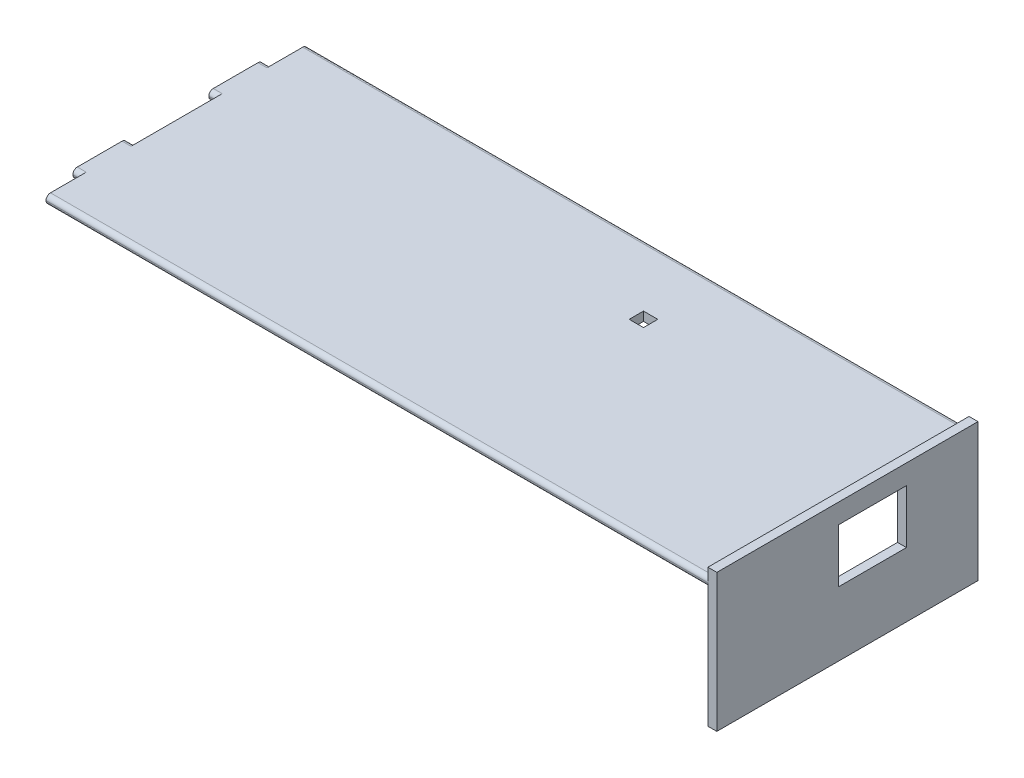
SolidWorks part; units mm, degrees
ref_plane "前视基准面" through (0, 0, 0) normal (0, 0, 1) x (1, 0, 0)
ref_plane "上视基准面" through (0, 0, 0) normal (0, 1, 0) x (1, 0, 0)
ref_plane "右视基准面" through (0, 0, 0) normal (1, 0, 0) x (0, 0, -1)
other "Configuration Table"
sketch "草图1" plane through (0, 0, 0) normal (0, 1, 0) x (1, 0, 0)
  line L1 (-87.0065, 44.1075) -> (97.9935, 44.1075)
  line L2 (-87.0065, 44.1075) -> (-87.0065, -28.8925)
  line L3 (-87.0065, -28.8925) -> (97.9935, -28.8925)
  line L4 (97.9935, 44.1075) -> (97.9935, -28.8925)
  dimension "D1" = 185
  dimension "D2" = 73
extrude "凸台-拉伸1" add sketch "草图1" along normal blind 2.5
sketch "草图2" plane through (-87.0065, 0, 0) normal (-1, 0, 0) x (0, 0, 1)
  line L0 (-44.1075, 2.5) -> (28.8925, 2.5) construction
  line L1 (-34.1075, 2.5) -> (-19.1075, 2.5)
  line L2 (-34.1075, 2.5) -> (-34.1075, 0)
  line L3 (-34.1075, 0) -> (-19.1075, 0)
  line L4 (-19.1075, 2.5) -> (-19.1075, 0)
  line L5 (-44.1075, 0) -> (28.8925, 0) construction
  line L6 (-44.1075, 2.5) -> (-44.1075, 0) construction
  line L7 (3.8925, 2.5) -> (18.8925, 2.5)
  line L8 (3.8925, 2.5) -> (3.8925, 0)
  line L9 (3.8925, 0) -> (18.8925, 0)
  line L10 (18.8925, 2.5) -> (18.8925, 0)
  line L11 (28.8925, 2.5) -> (28.8925, 0) construction
  dimension "D1" = 10
  dimension "D2" = 15
  dimension "D3" = 15
  dimension "D4" = 10
extrude "凸台-拉伸2" add sketch "草图2" along normal blind 2.5
fillet "圆角2" radius 1.25 8 edges at (-88.2565, 2.5, 3.8925) (-88.2565, 0, 3.8925) (-88.2565, 0, 18.8925) (-88.2565, 2.5, 18.8925) (-88.2565, 0, -34.1075) (-88.2565, 2.5, -19.1075) (-88.2565, 0, -19.1075) (-88.2565, 2.5, -34.1075)
sketch "草图3" plane through (97.9935, 0, 0) normal (1, 0, 0) x (0, 0, -1)
  line L0 (-28.8925, 2.5) -> (44.1075, 2.5) construction
  line L1 (-28.8925, 5) -> (44.1075, 5)
  line L2 (-28.8925, 5) -> (-28.8925, -33.5)
  line L3 (-28.8925, -33.5) -> (44.1075, -33.5)
  line L4 (44.1075, 5) -> (44.1075, -33.5)
  dimension "D1" = 2.5
  dimension "D2" = 73
  dimension "D3" = 38.5
extrude "凸台-拉伸3" add sketch "草图3" along normal blind 2.5
fillet "圆角3" radius 1.25 4 edges at (5.4935, 0, -44.1075) (5.4935, 2.5, -44.1075) (5.4935, 0, 28.8925) (5.4935, 2.5, 28.8925)
sketch "草图4" plane through (100.4935, 0, 0) normal (1, 0, 0) x (0, 0, -1)
  line L0 (-28.8925, -33.5) -> (44.1075, -33.5) construction
  line L1 (5.1075, -0.5) -> (24.1075, -0.5)
  line L2 (5.1075, -0.5) -> (5.1075, -15.5)
  line L3 (5.1075, -15.5) -> (24.1075, -15.5)
  line L4 (24.1075, -0.5) -> (24.1075, -15.5)
  line L6 (44.1075, -33.5) -> (44.1075, 5) construction
  dimension "D1" = 19
  dimension "D2" = 15
  dimension "D3" = 18
  dimension "D4" = 20
extrude "切除-拉伸1" cut sketch "草图4" against normal blind 2.5
sketch "草图5" plane through (0, 2.5, 0) normal (0, 1, 0) x (1, 0, 0)
  line L0 (97.9935, 44.1075) -> (97.9935, -28.8925) construction
  line L1 (24.4935, 26.6075) -> (28.4935, 26.6075)
  line L2 (24.4935, 26.6075) -> (24.4935, 22.6075)
  line L3 (24.4935, 22.6075) -> (28.4935, 22.6075)
  line L4 (28.4935, 26.6075) -> (28.4935, 22.6075)
  line L5 (97.9935, -27.6425) -> (97.9935, 42.8575) construction
  line L7 (100.4935, 44.1075) -> (97.9935, 44.1075) construction
  dimension "D1" = 69.5
  dimension "D2" = 73.5
  dimension "D3" = 17.5
  dimension "D4" = 4
extrude "切除-拉伸2" cut sketch "草图5" against normal blind 2.5
